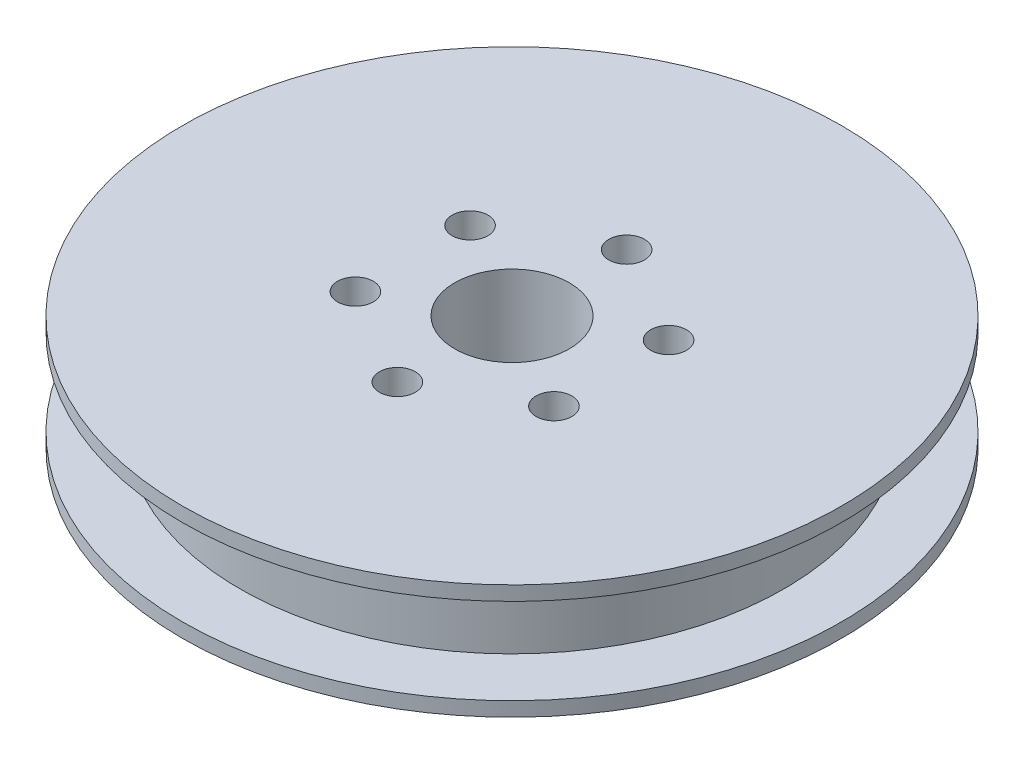
SolidWorks part; units mm, degrees
ref_plane "Front Plane" through (0, 0, 0) normal (0, 0, 1) x (1, 0, 0)
ref_plane "Top Plane" through (0, 0, 0) normal (0, 1, 0) x (1, 0, 0)
ref_plane "Right Plane" through (0, 0, 0) normal (1, 0, 0) x (0, 0, -1)
sketch "Sketch2" plane through (0, 0, 0) normal (0, 1, 0) x (1, 0, 0)
  circle A0 centre (0, 0) radius 60.325
  circle A1 centre (0, 0) radius 25.4
  circle A2 centre (0, 25.4) radius 3.9688
  circle A3 centre (21.997, 12.7) radius 3.9688
  circle A4 centre (21.997, -12.7) radius 3.9688
  circle A5 centre (0, -25.4) radius 3.9688
  circle A6 centre (-21.997, -12.7) radius 3.9688
  circle A7 centre (-21.997, 12.7) radius 3.9688
  circle A8 centre (0, 0) radius 12.7
  point P19 (0, 0)
  dimension "D2" = 120.65
  dimension "D3" = 50.8
  dimension "D4" = 7.9375
  dimension "D5" = 25.4
  dimension "D1" = 6
extrude "Boss-Extrude1" add sketch "Sketch2" along normal blind 19.05 contours A0 A7 A1 A2 A3 A4 A5 A6 | A7 A1 A6 A5 A4 A3 A2 region at (-58.6188, 0, 0) region at (24.2711, 0, 4.5068)
sketch "Sketch3" plane through (0, 19.05, 0) normal (0, 1, 0) x (1, 0, 0)
  circle A0 centre (0, 25.4) radius 3.9688 construction
  circle A1 centre (21.997, 12.7) radius 3.9688 construction
  circle A2 centre (21.997, -12.7) radius 3.9688 construction
  circle A3 centre (0, -25.4) radius 3.9688 construction
  circle A4 centre (-21.997, -12.7) radius 3.9688 construction
  circle A5 centre (0, 0) radius 12.7 construction
  circle A6 centre (-21.997, 12.7) radius 3.9688 construction
  circle A7 centre (0, 25.4) radius 3.9688
  circle A8 centre (21.997, 12.7) radius 3.9688
  circle A9 centre (21.997, -12.7) radius 3.9688
  circle A10 centre (0, -25.4) radius 3.9688
  circle A11 centre (-21.997, -12.7) radius 3.9688
  circle A12 centre (0, 0) radius 12.7
  circle A13 centre (-21.997, 12.7) radius 3.9688
  circle A14 centre (0, 0) radius 73.025
  dimension "D1" = 146.05
extrude "Boss-Extrude2" add sketch "Sketch3" along normal blind 3.175
sketch "Sketch4" plane through (0, 0, 0) normal (0, -1, 0) x (1, 0, 0)
  circle A0 centre (0, 0) radius 12.7 construction
  circle A1 centre (-21.997, -12.7) radius 3.9688 construction
  circle A2 centre (0, -25.4) radius 3.9688 construction
  circle A3 centre (21.997, -12.7) radius 3.9688 construction
  circle A4 centre (21.997, 12.7) radius 3.9688 construction
  circle A5 centre (0, 25.4) radius 3.9688 construction
  circle A6 centre (-21.997, 12.7) radius 3.9688 construction
  circle A7 centre (0, 0) radius 12.7
  circle A8 centre (-21.997, -12.7) radius 3.9688
  circle A9 centre (0, -25.4) radius 3.9688
  circle A10 centre (21.997, -12.7) radius 3.9688
  circle A11 centre (21.997, 12.7) radius 3.9688
  circle A12 centre (0, 25.4) radius 3.9688
  circle A13 centre (-21.997, 12.7) radius 3.9688
  circle A14 centre (0, 0) radius 73.025 construction
  circle A15 centre (0, 0) radius 73.025
extrude "Boss-Extrude3" add sketch "Sketch4" along normal blind 3.175
